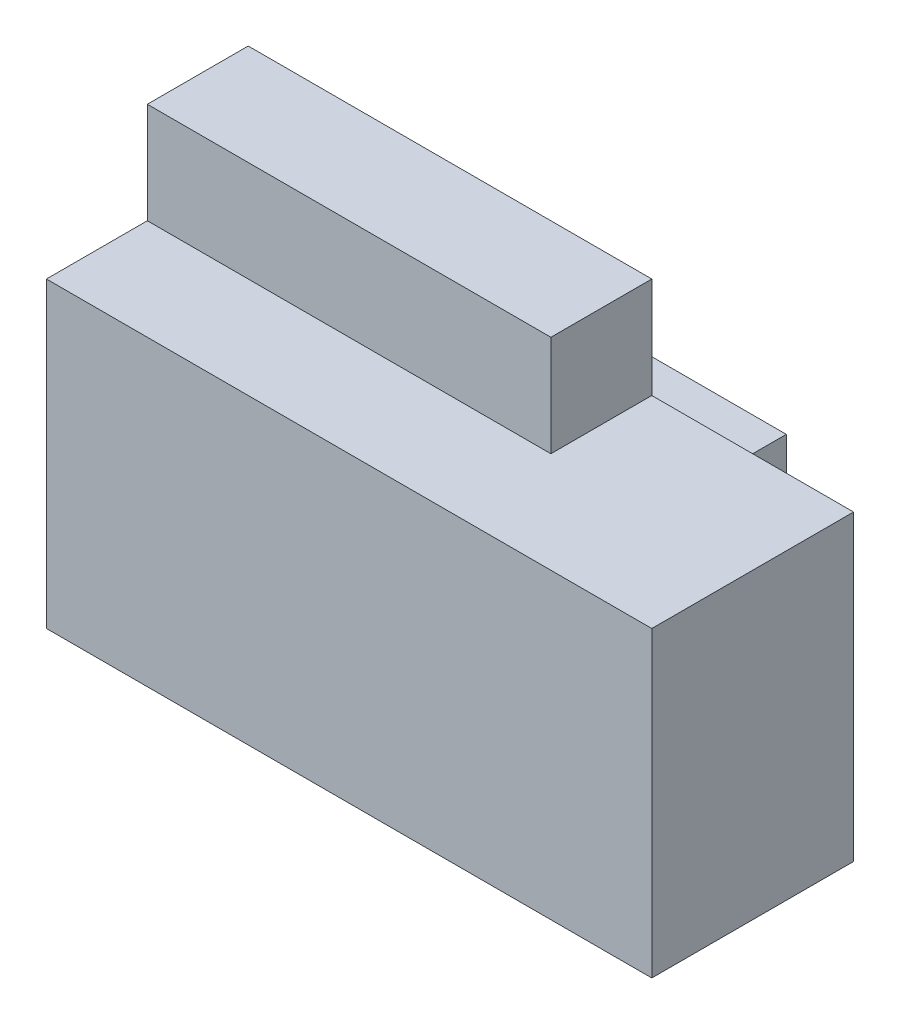
SolidWorks part; units mm, degrees
ref_plane "Front Plane" through (0, 0, 0) normal (0, 0, 1) x (1, 0, 0)
ref_plane "Top Plane" through (0, 0, 0) normal (0, 1, 0) x (1, 0, 0)
ref_plane "Right Plane" through (0, 0, 0) normal (1, 0, 0) x (0, 0, -1)
sketch "Sketch1" plane through (0, 0, 0) normal (0, 1, 0) x (1, 0, 0)
  line L1 (0, 0) -> (72, 0)
  line L2 (0, 0) -> (0, 24)
  line L3 (0, 24) -> (72, 24)
  line L4 (72, 0) -> (72, 24)
  line L5 (0, 24) -> (48, 24)
  line L6 (0, 24) -> (0, 12)
  line L7 (0, 12) -> (48, 12)
  line L8 (48, 24) -> (48, 12)
  line L9 (0, 24) -> (48, 24)
  line L10 (0, 24) -> (0, 40)
  line L11 (0, 40) -> (48, 40)
  line L12 (48, 24) -> (48, 40)
  dimension "D1" = 24
  dimension "D2" = 48
  dimension "D3" = 72
  dimension "D4" = 48
  dimension "D5" = 12
  dimension "D6" = 40
extrude "Boss-Extrude1" add sketch "Sketch1" along normal blind 36 contours L3 L8 L7 L2 L1 L4 region at (42, 0, -9)
extrude "Boss-Extrude2" add sketch "Sketch1<3>" along normal blind 48 contours L8 L3 L2 L7 region at (24, 0, -18)
sketch "Sketch1<3>" plane through (0, 0, 0) normal (0, 1, 0) x (1, 0, 0) same geometry as "Sketch1"
extrude "Boss-Extrude3" add sketch "Sketch1<4>" along normal blind 24 contours L3 L12 L11 L10 region at (24, 0, -32)
sketch "Sketch1<4>" plane through (0, 0, 0) normal (0, 1, 0) x (1, 0, 0) same geometry as "Sketch1"
